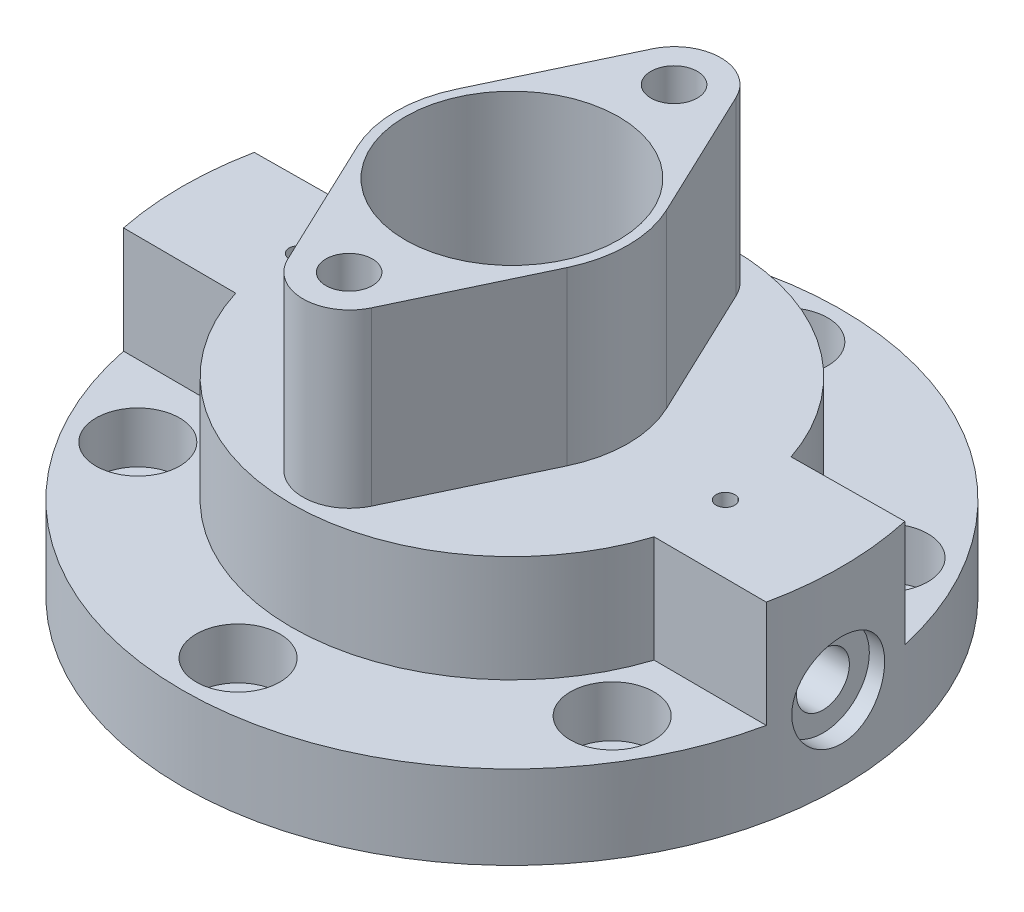
SolidWorks part; units mm, degrees
ref_plane "Front Plane" through (0, 0, 0) normal (0, 0, 1) x (1, 0, 0)
ref_plane "Top Plane" through (0, 0, 0) normal (0, 1, 0) x (1, 0, 0)
ref_plane "Right Plane" through (0, 0, 0) normal (1, 0, 0) x (0, 0, -1)
sketch "Sketch1" plane through (0, 0, 0) normal (0, 1, 0) x (1, 0, 0)
  line L0 (22.5169, 7.5531) -> (34.6633, 7.6618)
  line L1 (-34.7949, -7.0402) -> (-22.6664, -7.0922)
  line L2 (-34.7949, 7.0402) -> (-22.6485, 7.1489)
  line L3 (22.6048, -7.2861) -> (34.7333, -7.338)
  circle A0 centre (0, 0) radius 35.5
  arc A1 (-22.6664, -7.0922) -> (22.6048, -7.2861) centre (0, 0) ccw
  arc A2 (22.5169, 7.5531) -> (-22.6485, 7.1489) centre (0, 0) ccw
  point P4 (0, 0)
  point P5 (0, 0)
  point P10 (0, 0)
  point P11 (0, 0)
  point P12 (0, 0)
  dimension "D1" = 71
  dimension "D2" = 47.5
  dimension "D3" = 15
extrude "Boss-Extrude1" add sketch "Sketch1" against normal blind 9 contours A1 L1 A0 L3 | L0 A2 L2 A0 L1 A1 L3 | A2 L0 A0 L2 region at (-0.2192, 0, -24.4996) region at (0.1266, 0, -0.0138) region at (-0.1488, 0, 34.7484)
extrude "Boss-Extrude2" add sketch "Sketch1<3>" along normal blind 11.5 contours L0 A2 L2 A0 L1 A1 L3 region at (0.1266, 0, -0.0138)
sketch "Sketch1<3>" plane through (0, 0, 0) normal (0, 1, 0) x (1, 0, 0) same geometry as "Sketch1"
sketch "Sketch2" plane through (0, 11.5, 0) normal (0, 1, 0) x (1, 0, 0)
  line L1 (-4.5175, 19.6429) -> (-11.2938, 5.3571)
  line L2 (4.5175, 19.6429) -> (11.2938, 5.3571)
  line L3 (4.5175, -19.6429) -> (11.2938, -5.3571)
  line L4 (-4.5175, -19.6429) -> (-11.2938, -5.3571)
  arc A0 (-11.2938, 5.3571) -> (-11.2938, -5.3571) centre (0, 0) ccw
  arc A1 (4.5175, 19.6429) -> (-4.5175, 19.6429) centre (0, 17.5) ccw
  circle A2 centre (0, 17.5) radius 2.5
  circle A3 centre (0, -17.5) radius 2.5
  arc A4 (4.5175, -19.6429) -> (-4.5175, -19.6429) centre (0, -17.5) cw
  arc A5 (11.2938, -5.3571) -> (11.2938, 5.3571) centre (0, 0) ccw
  dimension "D1" = 25
  dimension "D2" = 10
  dimension "D3" = 5
  dimension "D4" = 35
extrude "Boss-Extrude3" add sketch "Sketch2" along normal blind 18.5 contours L1 A0 L4 A4 L3 A5 L2 A1
sketch "Sketch3" plane through (0, 30, 0) normal (0, 1, 0) x (1, 0, 0)
  circle A0 centre (0, 17.4659) radius 2.5
  circle A1 centre (0, -17.5341) radius 2.5
  point P4 (0, 0)
  point P5 (0, 0)
  dimension "D1" = 5
  dimension "D2" = 5
  dimension "D3" = 35
extrude "Cut-Extrude1" cut sketch "Sketch3" against normal blind 7.5
sketch "Sketch4" plane through (0, 0, 0) normal (0, 1, 0) x (1, 0, 0)
  circle A0 centre (0, 29.5) radius 4.5
  circle A1 centre (0, 29.5) radius 2.75
  point P3 (0, 0)
  point P5 (0, 0)
  dimension "D1" = 5.5
  dimension "D2" = 9
  dimension "D3" = 29.5
extrude "Cut-Extrude2" cut sketch "Sketch4" against normal through all contours A1 region at (0, 0, -29.5)
extrude "Cut-Extrude3" cut sketch "Sketch4<3>" against normal blind 5.5
sketch "Sketch4<3>" plane through (0, 0, 0) normal (0, 1, 0) x (1, 0, 0) same geometry as "Sketch4"
pattern_circular "CirPattern1" count 6 over 360 about axis through (0, 11.5, 0) along (0, 1, 0) of "Cut-Extrude3", "Cut-Extrude2"
ref_plane "Plane1" through (35.5, 0, 0) normal (1, 0, 0) x (0, 0, -1)
sketch "Sketch5" plane through (35.5, 0, 0) normal (1, 0, 0) x (0, 0, -1)
  circle A0 centre (0, 0) radius 5
  circle A1 centre (0, 0) radius 2.85
  dimension "D1" = 5.7
  dimension "D2" = 10
extrude "Cut-Extrude4" cut sketch "Sketch5" against normal blind 2
extrude "Cut-Extrude5" cut sketch "Sketch5<2>" against normal blind 15 contours A1 region at (35.5, 0, 0)
sketch "Sketch5<2>" plane through (35.5, 0, 0) normal (1, 0, 0) x (0, 0, -1) same geometry as "Sketch5"
mirror "Mirror1" about plane through (0, 0, 0) normal (1, 0, 0) of "Cut-Extrude4", "Cut-Extrude5"
sketch "Sketch6" plane through (0, 11.5, 0) normal (0, 1, 0) x (1, 0, 0)
  circle A0 centre (23, 0) radius 1
  point P2 (0, 0)
  dimension "D1" = 2
  dimension "D2" = 23
extrude "Cut-Extrude6" cut sketch "Sketch6" against normal blind 12
mirror "Mirror2" about plane through (0, 0, 0) normal (1, 0, 0) of "Cut-Extrude6"
sketch "Sketch7" plane through (0, 0, 0) normal (1, 0, 0) x (0, 0, -1)
  line L0 (0, 30) -> (0, -9)
  line L1 (5.3571, 30) -> (-5.3571, 30) construction
  line L2 (-35.5, -9) -> (35.5, -9) construction
  line L3 (0, -9) -> (-15.5, -9)
  line L4 (-15.5, -9) -> (-15.5, 0)
  line L5 (-15.5, 0) -> (-13.1337, 0)
  line L6 (-13.1337, 0) -> (-10.9422, 8.1786)
  line L7 (-10.9422, 8.1786) -> (-7.3324, 8.1786)
  line L8 (-7.3324, 8.1786) -> (-7.3324, 11.5)
  line L9 (-7.3324, 11.5) -> (-11.5, 11.5)
  line L10 (-11.5, 11.5) -> (-11.5, 30)
  line L11 (-19.6429, 30) -> (-5.3571, 30) construction
  line L12 (-11.5, 30) -> (0, 30)
  dimension "D1" = 15.5
  dimension "D2" = 9
  dimension "D3" = 15
  dimension "D4" = 18.5
  dimension "D5" = 11.5
revolve "Cut-Revolve1" cut sketch "Sketch7" angle 360 about L0
